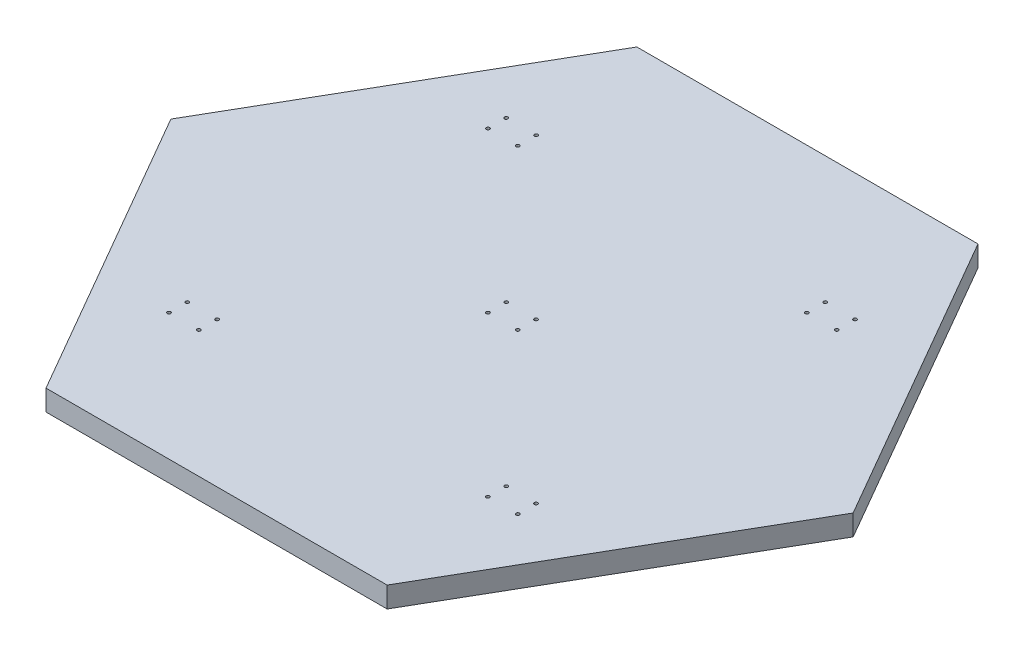
SolidWorks part; units mm, degrees
material "Plywood"
ref_plane "Front Plane" through (0, 0, 0) normal (0, 0, 1) x (1, 0, 0)
ref_plane "Top Plane" through (0, 0, 0) normal (0, 1, 0) x (1, 0, 0)
ref_plane "Right Plane" through (0, 0, 0) normal (1, 0, 0) x (0, 0, -1)
sketch "Sketch1" plane through (0, 0, 0) normal (0, 1, 0) x (1, 0, 0)
  line L38 (835.3235, 0) -> (417.6617, 723.4114)
  line L39 (417.6617, 723.4114) -> (-417.6617, 723.4114)
  line L40 (-417.6617, 723.4114) -> (-835.3235, 0)
  line L41 (-835.3235, 0) -> (-417.6617, -723.4114)
  line L42 (-417.6617, -723.4114) -> (417.6617, -723.4114)
  line L43 (417.6617, -723.4114) -> (835.3235, 0)
  line L44 (762, 0) -> (381, 659.9114)
  line L45 (381, 659.9114) -> (-381, 659.9114)
  line L46 (-381, 659.9114) -> (-762, 0)
  line L47 (-762, 0) -> (-381, -659.9114)
  line L48 (-381, -659.9114) -> (381, -659.9114)
  line L49 (381, -659.9114) -> (762, 0)
  line L50 (762, 0) -> (381, 659.9114) construction
  line L51 (381, 659.9114) -> (-381, 659.9114) construction
  line L52 (-381, 659.9114) -> (-762, 0) construction
  line L53 (-762, 0) -> (-381, -659.9114) construction
  line L54 (-381, -659.9114) -> (381, -659.9114) construction
  line L55 (381, -659.9114) -> (762, 0) construction
  dimension "D1" = 0
  dimension "D2" = 63.5
extrude "Boss-Extrude1" add sketch "Sketch1" against normal blind 50.8
sketch "Sketch5" plane through (0, 0, 0) normal (0, -1, 0) x (-1, 0, 0)
  line L0 (-390.525, 390.525) -> (390.525, 390.525) construction
  line L1 (-427.101, 412.877) -> (-353.949, 412.877) construction
  line L2 (-427.101, 412.877) -> (-427.101, 368.173) construction
  line L3 (-427.101, 368.173) -> (-353.949, 368.173) construction
  line L4 (-353.949, 412.877) -> (-353.949, 368.173) construction
  line L5 (-390.525, 390.525) -> (-390.525, -390.525) construction
  line L6 (0, 390.525) -> (0, 0) construction
  line L9 (-355.6, 412.877) -> (-352.298, 412.877) construction
  line L10 (-355.6, 417.068) -> (-352.298, 417.068) construction
  line L11 (-355.6, 408.686) -> (-352.298, 408.686) construction
  line L12 (0, 0) -> (390.525, 0) construction
  line L15 (355.6, 412.877) -> (352.298, 412.877) construction
  line L18 (355.6, 417.068) -> (352.298, 417.068) construction
  line L19 (355.6, 408.686) -> (352.298, 408.686) construction
  line L20 (353.949, 412.877) -> (353.949, 368.173) construction
  line L22 (427.101, 368.173) -> (353.949, 368.173) construction
  line L23 (390.525, 390.525) -> (-390.525, 390.525)
  line L24 (390.525, -390.525) -> (390.525, 390.525)
  line L25 (-390.525, -390.525) -> (390.525, -390.525)
  line L31 (-390.525, 390.525) -> (-390.525, -390.525)
  line L34 (390.525, 390.525) -> (-390.525, 390.525) construction
  line L37 (390.525, -390.525) -> (390.525, 390.525) construction
  line L44 (-390.525, -390.525) -> (390.525, -390.525) construction
  line L47 (-390.525, 390.525) -> (-390.525, -390.525) construction
  line L48 (427.101, 412.877) -> (427.101, 368.173) construction
  line L49 (427.101, 412.877) -> (353.949, 412.877) construction
  line L50 (-355.6, -412.877) -> (-352.298, -412.877) construction
  line L51 (-355.6, -417.068) -> (-352.298, -417.068) construction
  line L52 (-355.6, -408.686) -> (-352.298, -408.686) construction
  line L53 (355.6, -412.877) -> (352.298, -412.877) construction
  line L54 (355.6, -417.068) -> (352.298, -417.068) construction
  line L55 (355.6, -408.686) -> (352.298, -408.686) construction
  line L56 (427.101, -412.877) -> (353.949, -412.877) construction
  line L57 (427.101, -412.877) -> (427.101, -368.173) construction
  line L58 (-390.525, 390.525) -> (-390.525, -390.525) construction
  line L59 (427.101, -368.173) -> (353.949, -368.173) construction
  line L60 (353.949, -412.877) -> (353.949, -368.173) construction
  line L61 (-353.949, -412.877) -> (-353.949, -368.173) construction
  line L62 (-427.101, -368.173) -> (-353.949, -368.173) construction
  line L63 (-427.101, -412.877) -> (-427.101, -368.173) construction
  line L64 (-427.101, -412.877) -> (-353.949, -412.877) construction
  arc A2 (-355.6, 417.068) -> (-355.6, 408.686) centre (-355.6, 412.877) ccw construction
  arc A3 (-352.298, 408.686) -> (-352.298, 417.068) centre (-352.298, 412.877) ccw construction
  circle A8 centre (-353.949, 412.877) radius 4.191
  circle A9 centre (-427.101, 412.877) radius 4.191
  circle A10 centre (-427.101, 368.173) radius 4.191
  circle A11 centre (-353.949, 368.173) radius 4.191
  arc A12 (355.6, 417.068) -> (355.6, 408.686) centre (355.6, 412.877) cw construction
  arc A13 (352.298, 408.686) -> (352.298, 417.068) centre (352.298, 412.877) cw construction
  circle A14 centre (353.949, 368.173) radius 4.191
  circle A15 centre (427.101, 368.173) radius 4.191
  circle A16 centre (427.101, 412.877) radius 4.191
  circle A17 centre (353.949, 412.877) radius 4.191
  arc A18 (-355.6, -417.068) -> (-355.6, -408.686) centre (-355.6, -412.877) cw construction
  arc A19 (-352.298, -408.686) -> (-352.298, -417.068) centre (-352.298, -412.877) cw construction
  arc A20 (355.6, -417.068) -> (355.6, -408.686) centre (355.6, -412.877) ccw construction
  arc A21 (352.298, -408.686) -> (352.298, -417.068) centre (352.298, -412.877) ccw construction
  circle A22 centre (353.949, -412.877) radius 4.191
  circle A23 centre (427.101, -412.877) radius 4.191
  circle A24 centre (427.101, -368.173) radius 4.191
  circle A25 centre (353.949, -368.173) radius 4.191
  circle A26 centre (-353.949, -368.173) radius 4.191
  circle A27 centre (-427.101, -368.173) radius 4.191
  circle A28 centre (-427.101, -412.877) radius 4.191
  circle A29 centre (-353.949, -412.877) radius 4.191
  point P4 (-390.525, 390.525)
  point P5 (-390.525, 412.877)
  point P6 (-353.949, 390.525)
  point P18 (-353.949, 412.877)
  point P27 (353.949, 412.877)
  point P45 (390.525, 390.525)
  point P48 (-353.949, -412.877)
  point P55 (353.949, -412.877)
  point P76 (390.525, -390.525)
  point P77 (-390.525, -390.525)
  dimension "D4" = 11.684
  dimension "D1" = 44.704
  dimension "D2" = 73.152
  dimension "D3" = 8.382
  dimension "D5" = 0
extrude "Cut-Extrude1" cut sketch "Sketch5" along normal up to surface (50.8 mm away) up to face at (0, -50.8, 0)
sketch "Sketch6" plane through (0, -50.8, 0) normal (0, -1, 0) x (-1, 0, 0)
  line L1 (-36.576, -22.352) -> (36.576, -22.352) construction
  line L2 (-36.576, -22.352) -> (-36.576, 22.352) construction
  line L3 (-36.576, 22.352) -> (36.576, 22.352) construction
  line L4 (36.576, -22.352) -> (36.576, 22.352) construction
  line L5 (-36.576, -22.352) -> (36.576, 22.352) construction
  line L6 (-36.576, 22.352) -> (36.576, -22.352) construction
  circle A0 centre (-36.576, 22.352) radius 4.191
  circle A1 centre (36.576, 22.352) radius 4.191
  circle A2 centre (36.576, -22.352) radius 4.191
  circle A3 centre (-36.576, -22.352) radius 4.191
  circle A4 centre (-353.949, 368.173) radius 4.191 construction
  point P0 (0, 0)
  dimension "D1" = 44.704
  dimension "D2" = 73.152
extrude "Cut-Extrude2" cut sketch "Sketch6" against normal up to surface (50.8 mm away) up to face at (-353.949, 0, 408.686)
